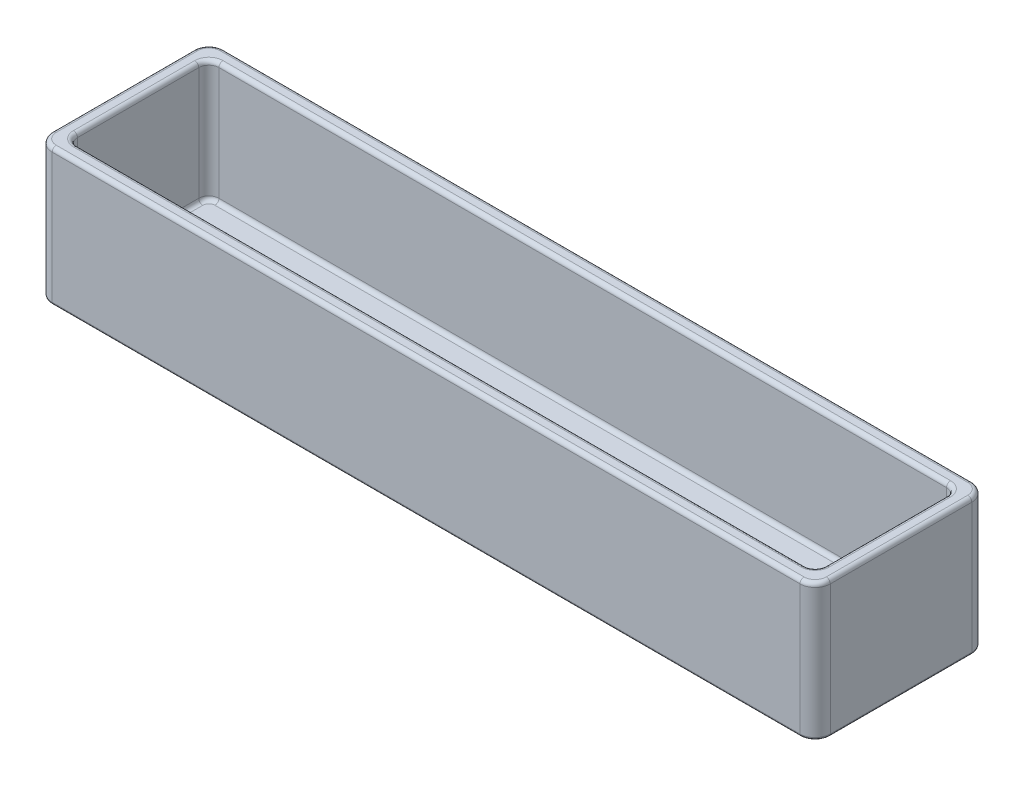
SolidWorks part; units mm, degrees
material "NEOPRENE"
ref_plane "Front" through (0, 0, 0) normal (0, 0, 1) x (1, 0, 0)
ref_plane "Top" through (0, 0, 0) normal (0, 1, 0) x (1, 0, 0)
ref_plane "Right" through (0, 0, 0) normal (1, 0, 0) x (0, 0, -1)
sketch "Sketch1" plane through (0, 0, 0) normal (0, 1, 0) x (1, 0, 0)
  line L0 (-117.475, 0) -> (-122.2375, 0) construction
  line L1 (-122.2375, 26.9875) -> (122.2375, 26.9875)
  line L2 (-122.2375, 26.9875) -> (-122.2375, -26.9875)
  line L3 (-122.2375, -26.9875) -> (122.2375, -26.9875)
  line L4 (122.2375, 26.9875) -> (122.2375, -26.9875)
  line L5 (-122.2375, 26.9875) -> (122.2375, -26.9875) construction
  line L6 (-122.2375, -26.9875) -> (122.2375, 26.9875) construction
  line L7 (117.475, 22.225) -> (-117.475, 22.225)
  line L8 (117.475, 22.225) -> (117.475, -22.225)
  line L9 (117.475, -22.225) -> (-117.475, -22.225)
  line L10 (-117.475, 22.225) -> (-117.475, -22.225)
  line L11 (117.475, 22.225) -> (-117.475, -22.225) construction
  line L12 (117.475, -22.225) -> (-117.475, 22.225) construction
  line L13 (0, 22.225) -> (0, 26.9875) construction
  point P0 (0, 0)
  point P6 (0, 0)
  dimension "D1" = 234.95
  dimension "D2" = 44.45
  dimension "THICKNESS" = 4.7625
extrude "Boss-Extrude1" add sketch "Sketch1" along normal blind 38.1
sketch "Sketch2" plane through (0, 0, 0) normal (0, -1, 0) x (1, 0, 0)
  line L4 (122.2375, -26.9875) -> (122.2375, 26.9875)
  line L5 (122.2375, 26.9875) -> (-122.2375, 26.9875)
  line L6 (-122.2375, 26.9875) -> (-122.2375, -26.9875)
  line L7 (-122.2375, -26.9875) -> (122.2375, -26.9875)
  line L8 (122.2375, -26.9875) -> (122.2375, 26.9875)
  line L9 (122.2375, 26.9875) -> (-122.2375, 26.9875)
  line L10 (-122.2375, 26.9875) -> (-122.2375, -26.9875)
  line L11 (-122.2375, -26.9875) -> (122.2375, -26.9875)
  arc A0 (105.9875, 2.6625) -> (105.9875, 6.8625) centre (105.9875, 4.7625) ccw construction
  arc A1 (105.9875, 6.8625) -> (105.9875, 2.6625) centre (105.9875, 4.7625) ccw construction
  arc A2 (74.9875, 2.6625) -> (74.9875, 6.8625) centre (74.9875, 4.7625) ccw construction
  arc A3 (74.9875, 6.8625) -> (74.9875, 2.6625) centre (74.9875, 4.7625) ccw construction
  arc A4 (105.9875, 2.6625) -> (105.9875, 6.8625) centre (105.9875, 4.7625) ccw
  arc A5 (105.9875, 6.8625) -> (105.9875, 2.6625) centre (105.9875, 4.7625) ccw
  arc A6 (74.9875, 2.6625) -> (74.9875, 6.8625) centre (74.9875, 4.7625) ccw
  arc A7 (74.9875, 6.8625) -> (74.9875, 2.6625) centre (74.9875, 4.7625) ccw
  dimension "D1" = 0
extrude "Boss-Extrude2" add sketch "Sketch2" along normal blind 4.7625
fillet "Fillet1" radius 3.175 4 edges at (117.475, 19.05, -22.225) (117.475, 19.05, 22.225) (-117.475, 19.05, 22.225) (-117.475, 19.05, -22.225)
fillet "Fillet2" radius 4.7625 4 edges at (-122.2375, 16.6687, -26.9875) (122.2375, 16.6687, -26.9875) (122.2375, 16.6687, 26.9875) (-122.2375, 16.6687, 26.9875)
sketch "Sketch4" plane through (0, -4.7625, 0) normal (0, -1, 0) x (1, 0, 0)
  line L2 (122.2375, -22.225) -> (122.2375, 22.225) construction
  line L3 (117.475, 26.9875) -> (-117.475, 26.9875) construction
  circle A0 centre (90.4875, 4.7625) radius 12.065
  dimension "D1" = 24.13
  dimension "D3" = 22.225
  dimension "D2" = 31.75
extrude "Cut-Extrude2" cut sketch "Sketch4" against normal through all
sketch "Sketch5" plane through (0, 0, -22.225) normal (0, 0, 1) x (1, 0, 0)
  line L0 (0, 0) -> (0, 19.05) construction
  line L1 (114.3, 38.1) -> (-114.3, 38.1) construction
  line L2 (-92.075, 0) -> (92.075, 0)
  line L3 (-92.075, 0) -> (-92.075, 38.1)
  line L4 (-92.075, 38.1) -> (92.075, 38.1)
  line L5 (92.075, 0) -> (92.075, 38.1)
  line L6 (-92.075, 0) -> (92.075, 38.1) construction
  line L7 (-92.075, 38.1) -> (92.075, 0) construction
  line L8 (114.3, 0) -> (-114.3, 0) construction
  dimension "D1" = 184.15
extrude "Boss-Extrude3" [suppressed] add sketch "Sketch5" along normal blind 1.651
fillet "Fillet3" [suppressed] radius 0.381
fillet "Fillet4" radius 1.27 8 edges at (116.5451, 0, -21.2951) (117.475, 0, 0) (116.5451, 0, 21.2951) (0, 0, 22.225) (-116.5451, 0, 21.2951) (-117.475, 0, 0) (-116.5451, 0, -21.2951) (0, 0, -22.225)
fillet "Fillet5" radius 0.762 8 edges at (-120.8426, -4.7625, 25.5926) (0, -4.7625, 26.9875) (120.8426, -4.7625, 25.5926) (122.2375, -4.7625, 0) (120.8426, -4.7625, -25.5926) (0, -4.7625, -26.9875) (-120.8426, -4.7625, -25.5926) (-122.2375, -4.7625, 0)
sketch "Sketch6" [suppressed] plane through (0, -4.7625, 0) normal (0, -1, 0) x (1, 0, 0)
  circle A0 centre (76.575, 6.35) radius 2.1 construction
  circle A1 centre (76.575, 6.35) radius 2.1
  circle A2 centre (107.575, 6.35) radius 2.1 construction
  circle A3 centre (107.575, 6.35) radius 2.1
extrude "Boss-Extrude4" [suppressed] add sketch "Sketch6" against normal up to surface (4.7625 mm away)
sketch "Sketch7" [suppressed] plane through (0, -4.7625, 0) normal (0, -1, 0) x (1, 0, 0)
  circle A0 centre (-45.2, 0.936) radius 4.445
  circle A1 centre (45, 0.936) radius 4.445
  dimension "D1" = 8.89
extrude "Cut-Extrude3" [suppressed] cut sketch "Sketch7" against normal through all
sketch "Sketch8" [suppressed] plane through (0, 38.1, 0) normal (0, 1, 0) x (1, 0, 0)
  line L25 (-156.7727, 50.8) -> (156.7727, 50.8)
  line L26 (-156.7727, 50.8) -> (-156.7727, -50.8)
  line L27 (-156.7727, -50.8) -> (156.7727, -50.8)
  line L28 (156.7727, 50.8) -> (156.7727, -50.8)
  line L29 (-156.7727, 50.8) -> (156.7727, -50.8) construction
  line L30 (-156.7727, -50.8) -> (156.7727, 50.8) construction
  point P15 (0, 0)
  dimension "D2" = 101.6
  dimension "D1" = 313.5454
extrude "Cut-Extrude4" [suppressed] cut sketch "Sketch8" against normal blind 9.525
sketch "Sketch9" [suppressed] plane through (0, 0, 0) normal (0, 1, 0) x (1, 0, 0)
  line L1 (141.011, 38.276) -> (-141.011, 38.276)
  line L2 (141.011, 38.276) -> (141.011, -38.276)
  line L3 (141.011, -38.276) -> (-141.011, -38.276)
  line L4 (-141.011, 38.276) -> (-141.011, -38.276)
  line L5 (141.011, 38.276) -> (-141.011, -38.276) construction
  line L6 (141.011, -38.276) -> (-141.011, 38.276) construction
  point P0 (0, 0)
  dimension "D1" = 76.552
  dimension "D2" = 282.022
extrude "Cut-Extrude5" [suppressed] cut sketch "Sketch9" along normal offset from surface 2.54 and the other way through all
sketch "Sketch10" [suppressed] plane through (0, 0, 0) normal (0, 1, 0) x (1, 0, 0)
  line L1 (-134.0132, -36.4455) -> (134.0132, -36.4455)
  line L2 (-134.0132, -36.4455) -> (-134.0132, 36.4455)
  line L3 (-134.0132, 36.4455) -> (134.0132, 36.4455)
  line L4 (134.0132, -36.4455) -> (134.0132, 36.4455)
  line L5 (-134.0132, -36.4455) -> (134.0132, 36.4455) construction
  line L6 (-134.0132, 36.4455) -> (134.0132, -36.4455) construction
  point P0 (0, 0)
  dimension "D1" = 268.0264
  dimension "D2" = 72.8909
extrude "Cut-Extrude6" [suppressed] cut sketch "Sketch10" along normal through all
sketch "Sketch11" [suppressed] plane through (0, -2.3368, 0) normal (0, -1, 0) x (1, 0, 0)
  line L1 (-127.2014, -33.7924) -> (127.2014, -33.7924)
  line L2 (-127.2014, -33.7924) -> (-127.2014, 33.7924)
  line L3 (-127.2014, 33.7924) -> (127.2014, 33.7924)
  line L4 (127.2014, -33.7924) -> (127.2014, 33.7924)
  line L5 (-127.2014, -33.7924) -> (127.2014, 33.7924) construction
  line L6 (-127.2014, 33.7924) -> (127.2014, -33.7924) construction
  point P0 (0, 0)
  dimension "D1" = 254.4028
  dimension "D2" = 67.5847
extrude "Cut-Extrude7" [suppressed] cut sketch "Sketch11" against normal offset from surface (37.8968 mm away) 2.54
sketch "Sketch12" [suppressed] plane through (0, 0, 0) normal (0, 1, 0) x (1, 0, 0)
  line L1 (-131.4623, -33.804) -> (131.4623, -33.804)
  line L2 (-131.4623, -33.804) -> (-131.4623, 33.804)
  line L3 (-131.4623, 33.804) -> (131.4623, 33.804)
  line L4 (131.4623, -33.804) -> (131.4623, 33.804)
  line L5 (-131.4623, -33.804) -> (131.4623, 33.804) construction
  line L6 (-131.4623, 33.804) -> (131.4623, -33.804) construction
  point P0 (0, 0)
  dimension "D1" = 262.9246
  dimension "D2" = 67.6081
extrude "Cut-Extrude8" [suppressed] cut sketch "Sketch12" along normal through all
sketch "Sketch13" [suppressed] plane through (0, 0, 22.225) normal (0, 0, -1) x (-1, 0, 0)
  line L0 (64.6891, 28.575) -> (64.6891, -4.7625)
  line L1 (114.3, 28.575) -> (-114.3, 28.575) construction
  line L2 (-117.475, -4.7625) -> (117.475, -4.7625) construction
  dimension "D1" = 33.3375
fillet "Fillet6" radius 1.27 16 edges at (116.5451, 38.1, -21.2951) (117.475, 38.1, 0) (116.5451, 38.1, 21.2951) (0, 38.1, 22.225) (-116.5451, 38.1, 21.2951) (-117.475, 38.1, 0) (-116.5451, 38.1, -21.2951) (120.8426, 38.1, -25.5926) (122.2375, 38.1, 0) (120.8426, 38.1, 25.5926) (0, 38.1, 26.9875) (-120.8426, 38.1, 25.5926) (-122.2375, 38.1, 0) (-120.8426, 38.1, -25.5926) (0, 38.1, -22.225) (0, 38.1, -26.9875)
fillet "Fillet7" [suppressed] radius 1.27
fillet "Fillet8" [suppressed] radius 1.27
fillet "Fillet9" radius 0.508 3 edges at (105.9875, 0, 2.6625) (74.9875, 0, 2.6625) (90.4875, 0, -7.3025)
sketch "Sketch14" plane through (0, 0, -26.9875) normal (0, 0, -1) x (-1, 0, 0)
  line L0 (0, -4.7625) -> (0, 38.1) construction
  line L1 (117.475, -4.7625) -> (-117.475, -4.7625) construction
  line L2 (-117.475, 38.1) -> (117.475, 38.1) construction
  line L3 (55.5625, 38.1) -> (-55.5625, -4.7625)
  line L4 (122.2375, 36.83) -> (122.2375, -4.0005) construction
  line L5 (55.5625, 38.1) -> (122.2375, 38.1)
  line L6 (122.2375, 38.1) -> (122.2375, -4.7625)
  line L7 (122.2375, -4.7625) -> (-55.5625, -4.7625)
  point P8 (0, 16.6687)
  dimension "D1" = 177.8
sketch "Sketch15" plane through (0, 0, -26.9875) normal (0, 0, -1) x (-1, 0, 0)
  line L4 (55.5625, 38.1) -> (-55.5625, -4.7625)
  line L5 (-55.5625, -4.7625) -> (122.2375, -4.7625)
  line L6 (122.2375, -4.7625) -> (122.2375, 38.1)
  line L7 (122.2375, 38.1) -> (55.5625, 38.1)
  line L8 (55.5625, 38.1) -> (-55.5625, -4.7625)
  line L9 (-55.5625, -4.7625) -> (122.2375, -4.7625)
  line L10 (122.2375, -4.7625) -> (122.2375, 38.1)
  line L11 (122.2375, 38.1) -> (55.5625, 38.1)
  dimension "D1" = 0
extrude "Cut-Extrude9" [suppressed] cut sketch "Sketch15" against normal through all
sketch "Sketch16" [suppressed] plane through (0, 0, -26.9875) normal (0, 0, -1) x (-1, 0, 0)
  line L0 (55.5625, 38.1) -> (-122.2375, 38.1)
  line L1 (-122.2375, 38.1) -> (-122.2375, -4.7625)
  line L2 (-122.2375, -4.7625) -> (-55.5625, -4.7625)
  line L3 (-122.2375, -4.0005) -> (-122.2375, 36.83) construction
  line L4 (55.5625, 38.1) -> (-55.5625, -4.7625)
  line L5 (-55.5625, -4.7625) -> (122.2375, -4.7625)
  line L6 (122.2375, -4.7625) -> (122.2375, 38.1)
  line L7 (122.2375, 38.1) -> (55.5625, 38.1)
  line L8 (55.5625, 38.1) -> (-55.5625, -4.7625)
  dimension "D1" = 0
extrude "Cut-Extrude10" [suppressed] cut sketch "Sketch16" against normal through all
sketch "Sketch17" [suppressed] plane through (0, 0, -26.9875) normal (0, 0, -1) x (-1, 0, 0)
  line L0 (0, 28.575) -> (0, -4.7625) construction
  line L1 (-117.475, 28.575) -> (117.475, 28.575) construction
  line L2 (117.475, -4.7625) -> (-117.475, -4.7625) construction
  line L3 (-55.5625, -4.7625) -> (55.5625, 28.575)
  line L4 (-122.2375, -4.0005) -> (-122.2375, 27.305) construction
  line L5 (55.5625, 28.575) -> (122.2375, 28.575)
  line L6 (122.2375, 28.575) -> (122.2375, -4.7625)
  line L7 (122.2375, -4.7625) -> (-55.5625, -4.7625)
  line L8 (122.2375, 27.305) -> (122.2375, -4.0005) construction
  point P8 (0, 11.9063)
  dimension "D1" = 177.8
sketch "Sketch18" [suppressed] plane through (0, 0, -26.9875) normal (0, 0, -1) x (-1, 0, 0)
  line L4 (55.5625, 28.575) -> (-55.5625, -4.7625)
  line L5 (122.2375, 28.575) -> (55.5625, 28.575)
  line L6 (122.2375, -4.7625) -> (122.2375, 28.575)
  line L7 (-55.5625, -4.7625) -> (122.2375, -4.7625)
  line L8 (55.5625, 28.575) -> (-55.5625, -4.7625)
  line L9 (122.2375, 28.575) -> (55.5625, 28.575)
  line L10 (122.2375, -4.7625) -> (122.2375, 28.575)
  line L11 (-55.5625, -4.7625) -> (122.2375, -4.7625)
  dimension "D1" = 0
extrude "Cut-Extrude11" [suppressed] cut sketch "Sketch18" against normal through all
sketch "Sketch19" [suppressed] plane through (0, 0, -26.9875) normal (0, 0, -1) x (-1, 0, 0)
  line L0 (-55.5625, -4.7625) -> (-122.2375, -4.7625)
  line L2 (-122.2375, -4.7625) -> (-122.2375, 28.575)
  line L3 (-122.2375, 28.575) -> (55.5625, 28.575)
  line L4 (55.5625, 28.575) -> (-55.5625, -4.7625)
  line L5 (122.2375, 28.575) -> (55.5625, 28.575)
  line L6 (122.2375, -4.7625) -> (122.2375, 28.575)
  line L7 (-55.5625, -4.7625) -> (122.2375, -4.7625)
  line L8 (55.5625, 28.575) -> (-55.5625, -4.7625)
  line L12 (-122.2375, -4.0005) -> (-122.2375, 27.305) construction
  dimension "D1" = 0
extrude "Cut-Extrude12" [suppressed] cut sketch "Sketch19" against normal through all and the other way blind 2.54
equation "\"D1@Boss-Extrude2\"=\"THICKNESS\""
